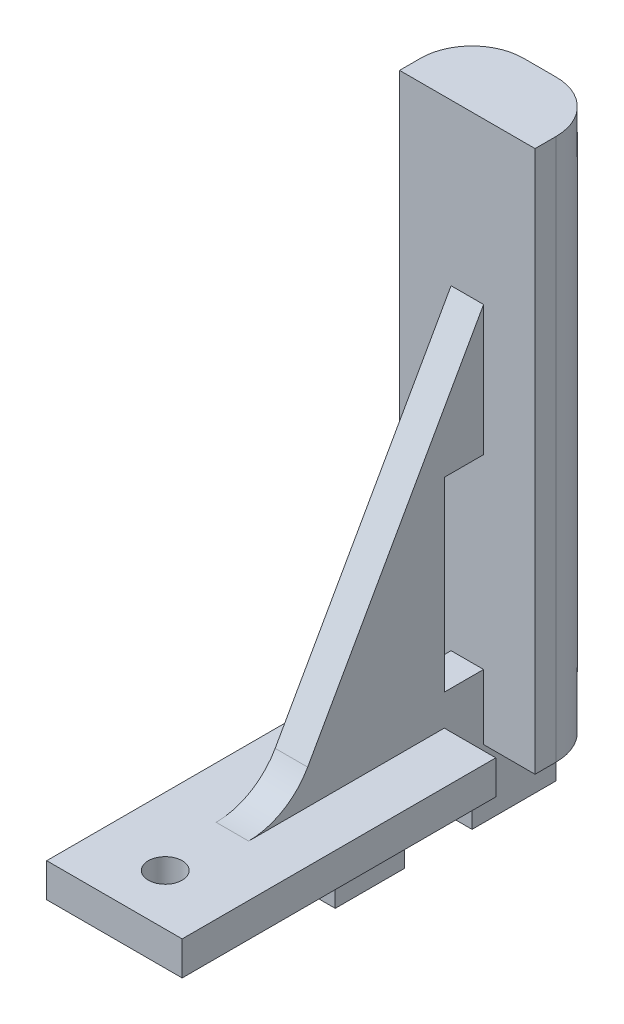
SolidWorks part; units mm, degrees
ref_plane "Front Plane" through (0, 0, 0) normal (0, 0, 1) x (1, 0, 0)
ref_plane "Top Plane" through (0, 0, 0) normal (0, 1, 0) x (1, 0, 0)
ref_plane "Right Plane" through (0, 0, 0) normal (1, 0, 0) x (0, 0, -1)
sketch "Sketch1" plane through (0, 0, 0) normal (1, 0, 0) x (0, 0, -1)
  line L0 (-19.939, 0) -> (19.939, 0)
  line L1 (19.939, 0) -> (19.939, 50.8)
  line L2 (19.939, 50.8) -> (13.1445, 50.8)
  line L3 (-19.939, 0) -> (-19.939, 3.175)
  line L5 (19.939, 0) -> (12.065, 0)
  line L6 (19.939, 0) -> (19.939, -6.35)
  line L7 (19.939, -6.35) -> (12.065, -6.35)
  line L8 (12.065, 0) -> (12.065, -6.35)
  line L9 (-0.762, 0) -> (5.715, 0)
  line L10 (-0.762, 0) -> (-0.762, -6.35)
  line L11 (-0.762, -6.35) -> (5.715, -6.35)
  line L12 (5.715, 0) -> (5.715, -6.35)
  line L13 (-32.8982, 3.175) -> (-19.939, 3.175) construction
  line L14 (11.303, 23.2833) -> (11.303, 35.9833) construction
  line L15 (9.7155, 6.35) -> (12.8905, 6.35) construction
  line L16 (9.7155, 6.35) -> (9.7155, 23.2833) construction
  line L17 (9.7155, 23.2833) -> (12.8905, 23.2833) construction
  line L18 (12.8905, 6.35) -> (12.8905, 23.2833) construction
  line L19 (9.7155, 35.9833) -> (12.8905, 35.9833) construction
  line L20 (9.7155, 35.9833) -> (9.7155, 52.9167) construction
  line L21 (9.7155, 52.9167) -> (12.8905, 52.9167) construction
  line L22 (12.8905, 35.9833) -> (12.8905, 52.9167) construction
  line L27 (11.303, 52.9167) -> (11.303, 65.6167) construction
  line L28 (9.4615, 6.096) -> (9.4615, 23.5373)
  line L29 (9.4615, 23.5373) -> (13.1445, 23.5373)
  line L30 (13.1445, 6.096) -> (13.1445, 23.5373)
  line L31 (9.4615, 6.096) -> (13.1445, 6.096)
  line L32 (9.4615, 35.7293) -> (9.4615, 53.1707)
  line L33 (9.4615, 53.1707) -> (13.1445, 53.1707)
  line L34 (13.1445, 35.7293) -> (13.1445, 53.1707)
  line L35 (9.4615, 35.7293) -> (13.1445, 35.7293)
  line L37 (13.1445, 50.8) -> (13.1445, 36.2585)
  line L38 (13.1445, 35.7293) -> (-5.1673, 3.175)
  line L39 (-5.1673, 3.175) -> (-19.939, 3.175)
  line L40 (9.4615, 23.5373) -> (6.2865, 23.5373) construction
  line L42 (9.4615, 6.096) -> (13.1445, 6.096)
  line L43 (9.4615, 6.096) -> (9.4615, 0)
  line L44 (9.4615, 0) -> (13.1445, 0)
  line L45 (13.1445, 6.096) -> (13.1445, 0)
  arc A2 (-19.939, 3.175) -> (13.1445, 36.2585) centre (-19.939, 36.2585) ccw
  point P3 (0, 0)
  point P8 (0, 0)
  point P16 (-15.1765, 0)
  point P44 (-20.7395, 4.7625)
  dimension "D1" = 3.175
  dimension "D2" = 7.874
  dimension "D3" = 6.35
  dimension "D4" = 6.477
  dimension "D5" = 6.35
  dimension "D6" = 4.7625
  dimension "D7" = 14.4145
  dimension "D9" = 50.8
  dimension "D11" = 3.175
  dimension "D12" = 3.175
  dimension "D13" = 7.0485
  dimension "D14" = 6.35
  dimension "D15" = 12.7
  dimension "D16" = 16.9333
  dimension "D17" = 0.254
  dimension "D18" = 0.254
extrude "Boss-Extrude1" add sketch "Sketch1" along normal mid plane 12.7 contours A2 L38 L39 L3 L0 L43 L28 | L45 L31 L43 L0 | A2 L28 L31 L30 L29 | A2 L29 L30 L45 L5 L1 L2 L34 L38 | L38 A2 L28 L29 | L28 A2 L29 region at (0, 5.7443, -0.298) region at (0, 21.1823, -6.7645) region at (0, 3.048, -11.303) region at (0, 25.4385, -16.4178) region at (0, 14.6351, -11.3365) region at (0, 22.7069, -9.8482)
extrude "Cut-Extrude2" cut sketch "Sketch1<4>" against normal through all both and the other way through all contours L28 L31 L30 L29 | L35 L34 | L28 A2 L29 region at (0, 14.6351, -11.3365) region at (0, 22.7069, -9.8482) region at (0, 35.8616, -13.1432)
sketch "Sketch1<4>" plane through (0, 0, 0) normal (1, 0, 0) x (0, 0, -1) same geometry as "Sketch1"
extrude "Boss-Extrude2" add sketch "Sketch1<3>" along normal mid plane 3.048 contours L0 L8 L7 L6 | L12 L0 L10 L11 region at (0, -3.175, -2.4765) region at (0, -3.175, -16.002)
sketch "Sketch1<3>" plane through (0, 0, 0) normal (1, 0, 0) x (0, 0, -1) same geometry as "Sketch1"
sketch "Sketch2" plane through (0, 0, 0) normal (0, -1, 0) x (1, 0, 0)
  circle A0 centre (0, 15.1765) radius 1.5875
  dimension "D1" = 3.175
extrude "Cut-Extrude1" cut sketch "Sketch2" against normal through all
fillet "Fillet1" radius 4.826 2 edges at (-6.35, 25.4, -19.939) (6.35, 25.4, -19.939)
fillet "Fillet2" radius 6.35 1 edges at (0, 3.175, 5.1673)
sketch "Sketch3" plane through (0, 0, 0) normal (1, 0, 0) x (0, 0, -1)
  line L0 (19.939, 50.8) -> (19.939, 0) construction
  line L1 (19.939, 38.1) -> (18.669, 38.1)
  line L2 (19.939, 38.1) -> (19.939, 28.575)
  line L3 (19.939, 28.575) -> (18.669, 28.575)
  line L4 (18.669, 38.1) -> (18.669, 28.575)
  line L5 (12.065, 0) -> (19.939, 0) construction
  dimension "D1" = 28.575
  dimension "D2" = 9.525
  dimension "D3" = 1.27
extrude "Cut-Extrude3" cut sketch "Sketch3" against normal through all both and the other way through all
sketch "Sketch4" plane through (0, 50.8, 0) normal (0, 1, 0) x (1, 0, 0)
  line L0 (1.524, 19.939) -> (-1.524, 19.939) construction
  line L1 (-6.35, -19.939) -> (6.35, -19.939)
  line L2 (-6.35, -19.939) -> (-6.35, 19.939)
  line L3 (-6.35, 19.939) -> (6.35, 19.939)
  line L4 (6.35, -19.939) -> (6.35, 19.939)
  line L5 (-1.524, 19.939) -> (-1.524, 12.065) construction
  line L6 (1.524, 19.939) -> (-1.524, 19.939)
  line L7 (1.524, 19.939) -> (1.524, -19.939)
  line L8 (1.524, -19.939) -> (-1.524, -19.939)
  line L9 (-1.524, 19.939) -> (-1.524, -19.939)
  line M9 (-6.35, 13.1445) -> (6.35, 13.1445)
extrude "Cut-Extrude5" cut sketch "Sketch4" against normal up to surface (47.625 mm away) contours L9 L2 L1 M9 | L7 L1 L4 M9 region at (-3.937, 50.8, 3.3972) region at (3.937, 50.8, 3.3972) up to face at (0, 3.175, 13.589)
sketch "Sketch5" plane through (6.35, 0, 0) normal (1, 0, 0) x (0, 0, -1)
  line L0 (12.065, 0) -> (19.939, 0) construction
  line L1 (9.4615, 6.096) -> (13.1445, 6.096)
  line L2 (9.4615, 6.096) -> (9.4615, 0)
  line L3 (9.4615, 0) -> (13.1445, 0)
  line L4 (13.1445, 6.096) -> (13.1445, 0)
  line L5 (13.1445, 3.175) -> (13.1445, 6.096) construction
  line L6 (13.1445, 3.175) -> (13.1445, 50.8) construction
  point P7 (13.3985, 5.842)
extrude "Cut-Extrude6" cut sketch "Sketch5" against normal up to surface (4.826 mm away) up to face at (1.524, 13.376, -7.464)
extrude "Cut-Extrude7" cut sketch "Sketch5<2>" along normal up to surface (-7.874 mm away) from surface up to face at (-1.524, 13.376, -7.464) starting at face at (-6.35, 17.9917, -2.7728)
sketch "Sketch5<2>" plane through (6.35, 0, 0) normal (1, 0, 0) x (0, 0, -1) same geometry as "Sketch5"
